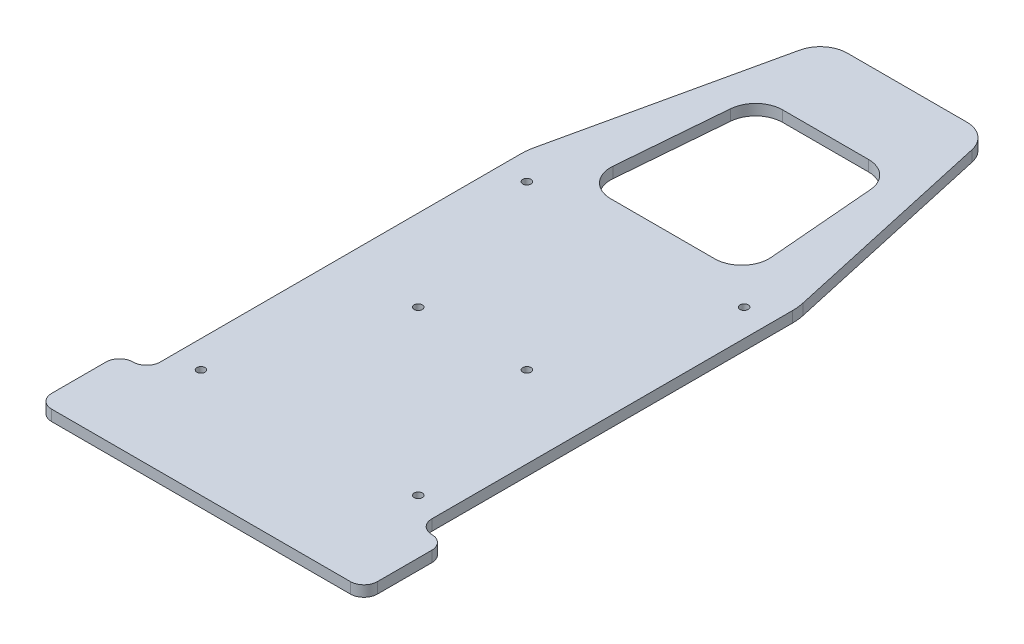
SolidWorks part; units mm, degrees
material "ПК/АБС"
ref_plane "Спереди" through (0, 0, 0) normal (0, 0, 1) x (1, 0, 0)
ref_plane "Сверху" through (0, 0, 0) normal (0, 1, 0) x (1, 0, 0)
ref_plane "Справа" through (0, 0, 0) normal (1, 0, 0) x (0, 0, -1)
sketch "Эскиз1" plane through (0, 0, 0) normal (0, 1, 0) x (1, 0, 0)
  line L0 (391.1853, -237.1173) -> (411.1853, -237.1173) construction
  line L1 (351.1853, -297.1173) -> (431.1853, -297.1173) construction
  line L2 (351.1853, -297.1173) -> (351.1853, -177.1173) construction
  line L3 (351.1853, -177.1173) -> (431.1853, -177.1173) construction
  line L4 (431.1853, -297.1173) -> (431.1853, -177.1173) construction
  line L5 (351.1853, -297.1173) -> (431.1853, -177.1173) construction
  line L6 (351.1853, -177.1173) -> (431.1853, -297.1173) construction
  line L7 (341.1853, -307.1173) -> (441.1853, -307.1173) construction
  line L8 (341.1853, -307.1173) -> (341.1853, -167.1173)
  line L9 (341.1853, -167.1173) -> (441.1853, -167.1173) construction
  line L10 (441.1853, -307.1173) -> (441.1853, -167.1173)
  line L11 (341.1853, -307.1173) -> (441.1853, -167.1173) construction
  line L12 (341.1853, -167.1173) -> (441.1853, -307.1173) construction
  line L13 (391.1853, -237.1173) -> (371.1853, -237.1173) construction
  line L14 (391.1853, -237.1173) -> (391.1853, -167.1173) construction
  line L15 (391.1853, -167.1173) -> (391.1853, -107.1173) construction
  line L16 (391.1853, -107.1173) -> (391.1853, -77.1173) construction
  line L17 (391.1853, -167.1173) -> (366.1853, -167.1173) construction
  line L18 (366.1853, -167.1173) -> (366.1853, -107.1173) construction
  line L19 (391.1853, -167.1173) -> (361.1853, -167.1173) construction
  line L20 (361.1853, -167.1173) -> (361.1853, -77.1173) construction
  line L21 (341.1853, -167.1173) -> (361.1853, -77.1173)
  line L22 (361.1853, -77.1173) -> (421.1853, -77.1173)
  line L23 (361.1853, -167.1173) -> (366.1853, -107.1173)
  line L24 (366.1853, -107.1173) -> (416.1853, -107.1173)
  line L25 (441.1853, -167.1173) -> (421.1853, -77.1173)
  line L26 (421.1853, -167.1173) -> (416.1853, -107.1173)
  line L27 (421.1853, -167.1173) -> (361.1853, -167.1173)
  line L28 (391.1853, -237.1173) -> (391.1853, -307.1173) construction
  line L29 (391.1853, -307.1173) -> (391.1853, -337.1173) construction
  line L30 (391.1853, -337.1173) -> (331.1853, -337.1173)
  line L31 (331.1853, -337.1173) -> (331.1853, -307.1173)
  line L32 (331.1853, -307.1173) -> (341.1853, -307.1173)
  line L33 (391.1853, -337.1173) -> (451.1853, -337.1173)
  line L34 (451.1853, -337.1173) -> (451.1853, -307.1173)
  line L35 (451.1853, -307.1173) -> (441.1853, -307.1173)
  circle A0 centre (351.1853, -177.1173) radius 1.5
  circle A1 centre (431.1853, -177.1173) radius 1.5
  circle A2 centre (431.1853, -297.1173) radius 1.5
  circle A3 centre (351.1853, -297.1173) radius 1.5
  circle A4 centre (371.1853, -237.1173) radius 1.5
  circle A5 centre (411.1853, -237.1173) radius 1.5
  point P0 (391.1853, -237.1173)
  point P10 (391.1853, -237.1173)
  dimension "D3" = 3
  dimension "D4" = 3
  dimension "D5" = 3
  dimension "D6" = 3
  dimension "D11" = 3
  dimension "D12" = 3
  dimension "D1" = 80
  dimension "D2" = 120
  dimension "D7" = 140
  dimension "D8" = 100
  dimension "D9" = 20
  dimension "D10" = 20
  dimension "D13" = 30
  dimension "D14" = 60
  dimension "D15" = 25
  dimension "D16" = 20
  dimension "D17" = 30
  dimension "D18" = 10
  dimension "D19" = 10
extrude "Бобышка-Вытянуть1" add sketch "Эскиз1" along normal blind 4
fillet "Скругление1" radius 5 6 edges at (441.1853, 2, 307.1173) (341.1853, 2, 307.1173) (331.1853, 2, 307.1173) (331.1853, 2, 337.1173) (451.1853, 2, 337.1173) (451.1853, 2, 307.1173)
fillet "Скругление2" radius 20 2 edges at (341.1853, 2, 167.1173) (441.1853, 2, 167.1173)
fillet "Скругление3" radius 10 4 edges at (366.1853, 2, 107.1173) (416.1853, 2, 107.1173) (421.1853, 2, 167.1173) (361.1853, 2, 167.1173)
fillet "Скругление4" radius 10 2 edges at (421.1853, 2, 77.1173) (361.1853, 2, 77.1173)
